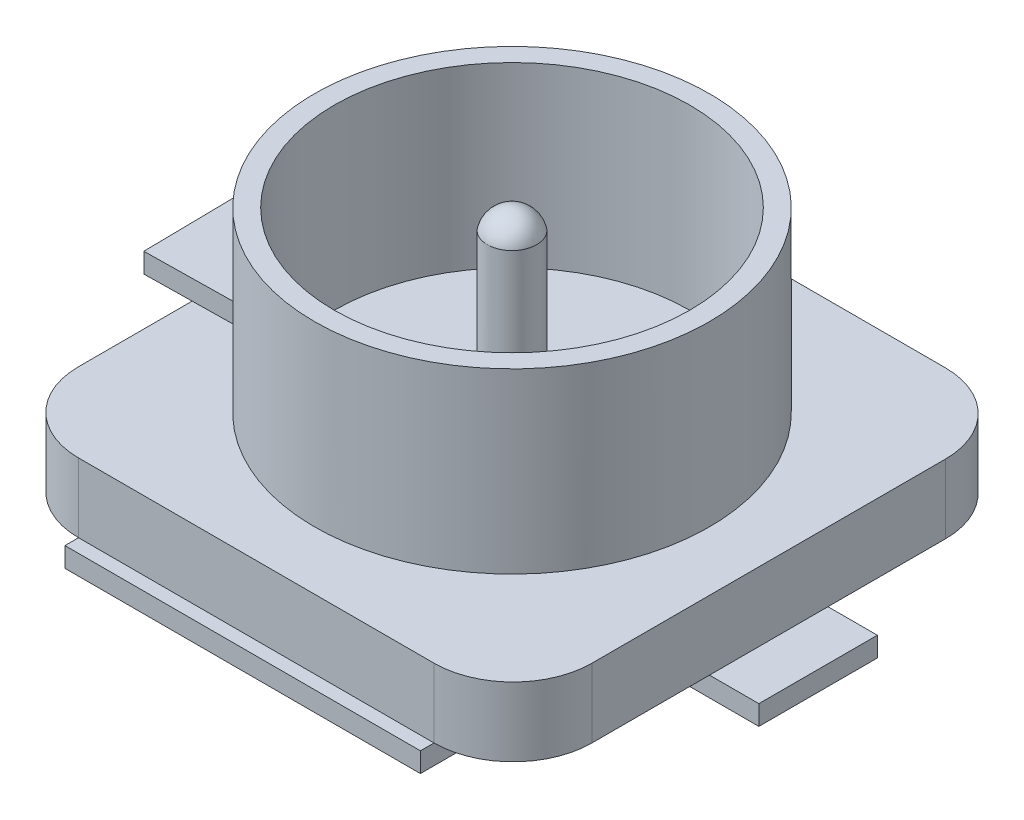
SolidWorks part; units mm, degrees
ref_plane "Спереди" through (0, 0, 0) normal (0, 0, 1) x (1, 0, 0)
ref_plane "Сверху" through (0, 0, 0) normal (0, 1, 0) x (1, 0, 0)
ref_plane "Справа" through (0, 0, 0) normal (1, 0, 0) x (0, 0, -1)
sketch "Sketch1" plane through (0, 0, 0) normal (0, 1, 0) x (1, 0, 0)
  line L0 (0, 255.3466) -> (0, -214.0784) construction
  line L1 (-211.4992, 0) -> (180.5481, 0) construction
  line L3 (-0.9, -1.295) -> (0.9, -1.295)
  line L4 (-1.3, -0.895) -> (-1.3, 0.895)
  line L5 (-0.9, 1.295) -> (0.9, 1.295)
  line L6 (1.3, -0.895) -> (1.3, 0.895)
  line L7 (-1.3, -1.295) -> (1.3, 1.295) construction
  line L8 (-1.3, 1.295) -> (1.3, -1.295) construction
  arc A0 (1.3, -0.895) -> (0.9, -1.295) centre (0.9, -0.895) cw
  arc A1 (-1.3, -0.895) -> (-0.9, -1.295) centre (-0.9, -0.895) ccw
  arc A2 (0.9, 1.295) -> (1.3, 0.895) centre (0.9, 0.895) cw
  arc A3 (-1.3, 0.895) -> (-0.9, 1.295) centre (-0.9, 0.895) cw
  point P5 (0, 0)
  dimension "D3" = 0.4
  dimension "D1" = 2.6
  dimension "D2" = 2.59
extrude "Boss-Extrude2" add sketch "Sketch1" along normal blind 0.35
sketch "Sketch2" plane through (0, 0.35, 0) normal (0, 1, 0) x (-1, 0, 0)
  circle A0 centre (0, 0) radius 1
  circle A1 centre (0, 0) radius 0.9
  dimension "D1" = 2
  dimension "D2" = 0.1
extrude "Boss-Extrude3" add sketch "Sketch2" along normal blind 0.9
sketch "Sketch3" plane through (0, 0.35, 0) normal (0, 1, 0) x (-1, 0, 0)
  circle A0 centre (0, 0) radius 0.125
  dimension "D1" = 0.25
extrude "Boss-Extrude4" add sketch "Sketch3" along normal blind 0.8
dome "Dome1" faces to dome 1 distance 0.1 reverse direction no elliptical dome no face at (0, 1.15, 0.125) parameters "D1"=0.1
sketch "Sketch4" plane through (0, 0, 0) normal (0, -1, 0) x (1, 0, 0)
  line L0 (0.9, 1.05) -> (0.9, 0) construction
  line L1 (0.9, 0) -> (0.9, -1.05) construction
  line L2 (-0.1438, 1.3638) -> (-0.1438, 0) construction
  line L3 (-0.9, 1.3638) -> (0.9, 1.3638)
  line L4 (-0.9, 1.3638) -> (-0.9, 1.05)
  line L5 (-0.9, 1.05) -> (0.9, 1.05)
  line L6 (0.9, 1.3638) -> (0.9, 1.05)
  line L7 (0, 1.725) -> (0, -1.8251) construction
  line L8 (-0.1438, 0) -> (-0.1438, -1.3638) construction
  line L9 (0, -1.3638) -> (0, 1.3638) construction
  line L10 (-0.9, -1.05) -> (0.9, -1.05)
  line L11 (-0.9, -1.05) -> (-0.9, -1.3638)
  line L12 (-0.9, -1.3638) -> (0.9, -1.3638)
  line L13 (0.9, -1.05) -> (0.9, -1.3638)
  line L19 (-1.6791, 0) -> (2.3362, 0) construction
  dimension "D1" = 2.1
  dimension "D2" = 1.8
extrude "Boss-Extrude5" add sketch "Sketch4" along normal blind 0.1
sketch "Sketch5" plane through (0, 0, 0) normal (0, -1, 0) x (1, 0, 0)
  line L0 (0, 0.3) -> (0, -0.3)
  line L1 (0, 0.3) -> (1.55, 0.3)
  line L2 (0, -0.3) -> (1.55, -0.3)
  line L3 (1.55, 0.3) -> (1.55, -0.3)
  line L4 (1.3, 0.895) -> (1.3, -0.895) construction
  circle A0 centre (0, 0) radius 0.4
  dimension "D1" = 0.8
  dimension "D2" = 0.6
  dimension "D3" = 0.25
extrude "Boss-Extrude6" add sketch "Sketch5" along normal blind 0.1 contours A0 | L2 L3 L1 L0
sketch "Sketch6" plane through (0, 0.35, 0) normal (0, 1, 0) x (1, 0, 0)
  line L0 (-0.8954, -0.3136) -> (-0.9044, 0.2864)
  line L1 (-0.8954, -0.3136) -> (-1.5409, -0.3234)
  line L2 (-0.9044, 0.2864) -> (-1.55, 0.2766)
  line L3 (-1.5409, -0.3234) -> (-1.55, 0.2766)
  line L4 (-1.3, 0.895) -> (-1.3, -0.895) construction
  circle A0 centre (0, 0) radius 0.9
  circle A1 centre (0, 0) radius 0.9 construction
  dimension "D3" = 0
  dimension "D1" = 0.25
  dimension "D2" = 0.6
extrude "Boss-Extrude7" add sketch "Sketch6" along normal blind 0.1 contours L3 L2 L0 L1
